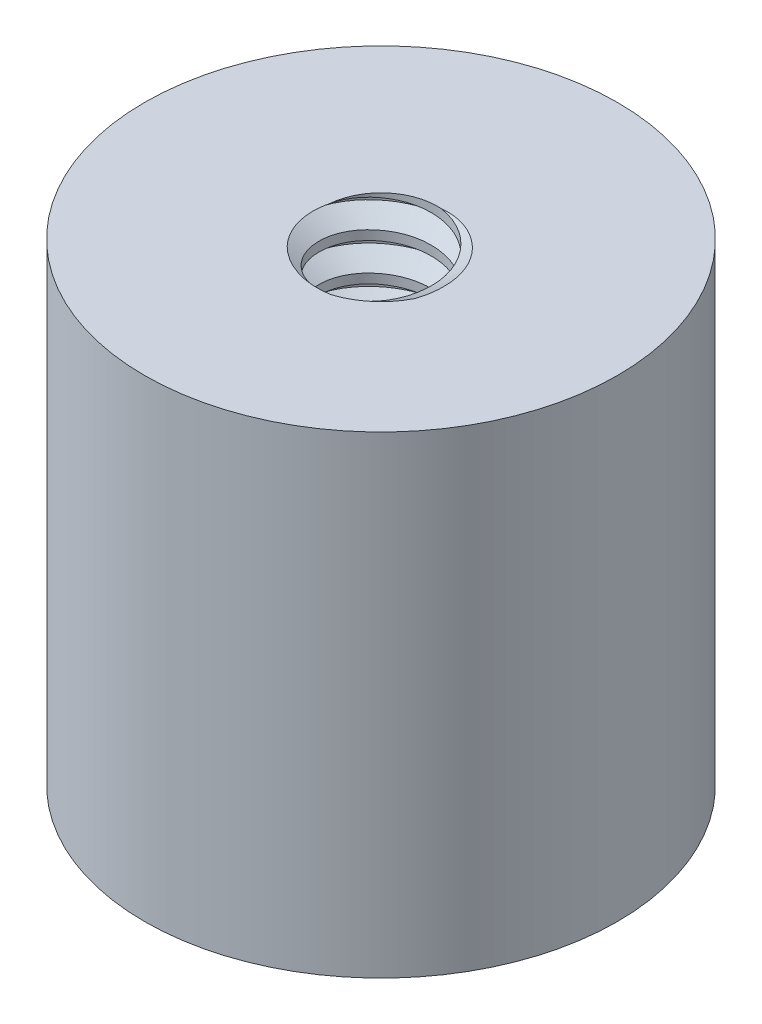
SolidWorks part; units mm, degrees
other "ThreadedCap" parameters "D1"=19.3475, "D2"=4.1976
ref_plane "Front Plane" through (0, 0, 0) normal (0, 0, 1) x (1, 0, 0)
ref_plane "Top Plane" through (0, 0, 0) normal (0, 1, 0) x (1, 0, 0)
ref_plane "Right Plane" through (0, 0, 0) normal (1, 0, 0) x (0, 0, -1)
sketch "Sketch1" plane through (0, 0, 0) normal (0, 1, 0) x (1, 0, 0)
  circle A0 centre (0, 0) radius 4
  circle A1 centre (0, 0) radius 1.3
  dimension "D1" = 2.6
  dimension "D2" = 8
extrude "Boss-Extrude1" add sketch "Sketch1" along normal blind 8
thread "Thread1" pitch 0.635 method extrude profile "Thread Profile1" start angle 0, offset 1, length 0, pitch 0.635, diameter 2.6
ref_plane "Plane1" through (-1.3, 9, 0) normal (0, 0, 1) x (-1, 0, 0)
sketch "Thread Profile1" plane through (-1.3, 9, 0) normal (0, 0, 1) x (-1, 0, 0)
  line L0 (0, 0) -> (0, 0.635) construction
  line L11 (0, 0) -> (0, 0.5556)
  line L12 (0, 0.5556) -> (-0.3437, 0.3572)
  line L13 (-0.3437, 0.3572) -> (-0.3437, 0.1984)
  line L15 (-0.3437, 0.1984) -> (0, 0)
  line L17 (-0.3437, 0.2778) -> (0, 0.2778) construction
  point P2 (0, 0)
  dimension "Pitch" = 0.635
  dimension "Profile_Angle" = 60
  dimension "Profile_Land" = 0.1588
  dimension "Profile_Height" = 0.3437
sketch "Sketch4" plane through (0, 8, 0) normal (0, 1, 0) x (1, 0, 0)
  circle A0 centre (0, 0) radius 4
extrude "Cut-Extrude1" cut sketch "Sketch4" along normal blind 8
sketch "Sketch5" plane through (0, 0, 0) normal (0, -1, 0) x (1, 0, 0)
  circle A0 centre (0, 0) radius 4
extrude "Cut-Extrude2" cut sketch "Sketch5" along normal blind 8
equation "\"syringeID\"= 8"
equation "\"driverOD\"= 2.6"
equation "\"threadedCapHeight\"= 8"
equation "\"D1@Sketch1\"=\"driverOD\""
equation "\"D2@Sketch1\"=\"syringeID\""
equation "\"D1@Boss-Extrude1\"=\"threadedCapHeight\""
